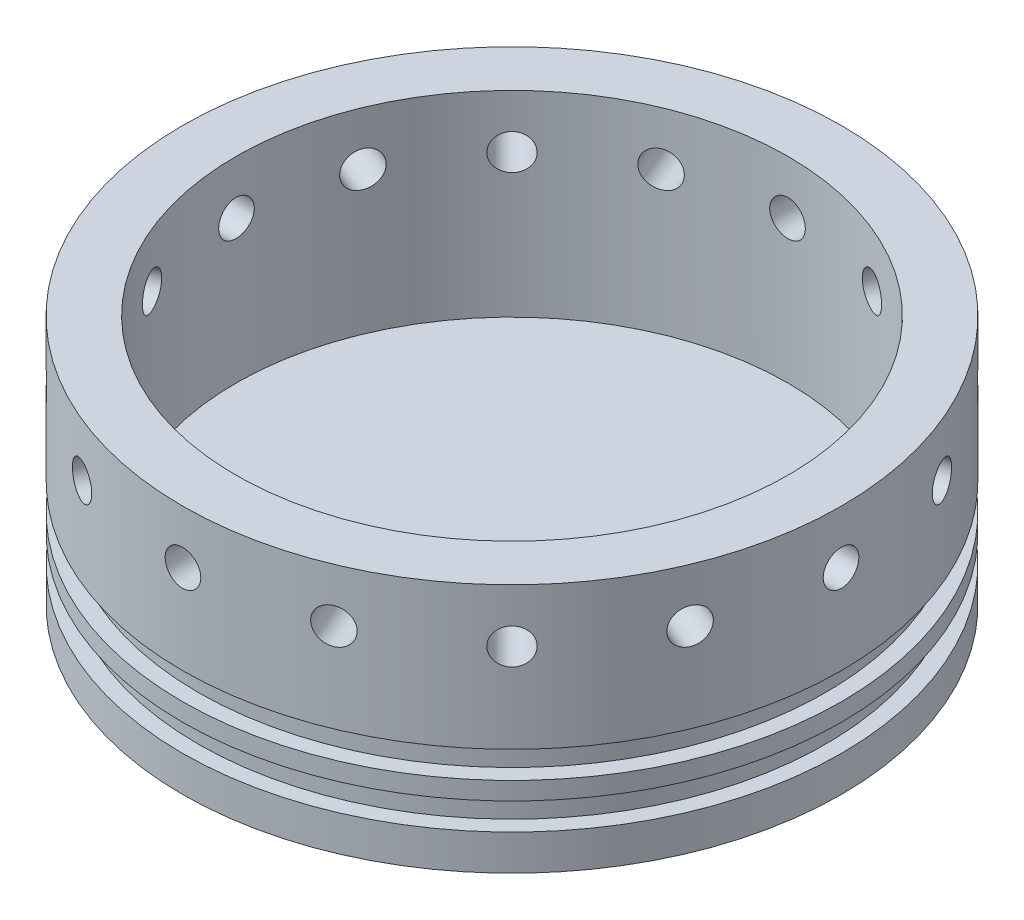
SolidWorks part; units mm, degrees
material "6061-T6 (SS)"
ref_plane "Front Plane" through (0, 0, 0) normal (0, 0, 1) x (1, 0, 0)
ref_plane "Top Plane" through (0, 0, 0) normal (0, 1, 0) x (1, 0, 0)
ref_plane "Right Plane" through (0, 0, 0) normal (1, 0, 0) x (0, 0, -1)
sketch "Sketch1" plane through (0, 0, 0) normal (0, 0, 1) x (1, 0, 0)
  line L1 (0, 0) -> (58.7375, 0)
  line L2 (58.7375, 0) -> (58.7375, 50.8) construction
  line L3 (0, 44.5262) -> (9.525, 44.5262)
  line L4 (58.7375, 0) -> (58.7375, 9.525)
  line L5 (58.7375, 9.525) -> (9.525, 9.525)
  line L6 (9.525, 9.525) -> (9.525, 44.5262)
  line L8 (0, 0) -> (0, 6.35)
  line L9 (0, 6.35) -> (2.8194, 6.35)
  line L10 (2.8194, 6.35) -> (2.8194, 11.1506)
  line L11 (2.8194, 11.1506) -> (0, 11.1506)
  line L15 (0, 11.1506) -> (0, 14.3256)
  line L16 (0, 14.3256) -> (2.8194, 14.3256)
  line L17 (2.8194, 14.3256) -> (2.8194, 19.1262)
  line L18 (2.8194, 19.1262) -> (0, 19.1262)
  line L19 (0, 19.1262) -> (0, 44.5262)
  dimension "D1" = 3.175
  dimension "D2" = 58.7375
  dimension "D3" = 9.525
  dimension "D4" = 6.35
  dimension "D5" = 4.8006
  dimension "D6" = 2.8194
  dimension "D7" = 4.8006
  dimension "D8" = 2.8194
  dimension "D9" = 2.8194
  dimension "D10" = 25.4
  dimension "D11" = 9.525
revolve "Revolve1" add sketch "Sketch1" angle 360 about L2 region at (0.7371, 3.175, 0)
ref_plane "HoleReferencePlane" through (0, 0, 58.7375) normal (0, 0, 1) x (1, 0, 0)
sketch "HoleReferencePoint" plane through (0, 0, 58.7375) normal (0, 0, 1) x (1, 0, 0)
  line L0 (107.95, 44.5262) -> (9.525, 44.5262) construction
  point P0 (58.7375, 35.0012)
  dimension "D1" = 9.525
hole_wizard "ForwardClosureHoles" positions "Sketch3" profile "Sketch5" hole size "1/4" standard "ANSI Inch" end condition through all
sketch "Sketch3" plane through (0, 0, 58.7375) normal (0, 0, 1) x (1, 0, 0)
  point P0 (58.7375, 35.0012)
sketch "Sketch5" plane through (58.7375, 35.0012, 58.7375) normal (1, 0, 0) x (0, -1, 0)
  line L0 (0, 0) -> (0, 117.475)
  line L1 (0, 117.475) -> (3.175, 117.475)
  line L2 (3.175, 117.475) -> (3.175, 0)
  line L5 (3.175, 0) -> (0, 0)
  line L11 (0, -6.35) -> (0, 107.95) construction
  dimension "Thru Hole Dia." = 6.35
  dimension "Thru Hole Depth" = 117.475
sketch "Centerline" plane through (0, 0, 0) normal (0, 0, 1) x (1, 0, 0)
  line L0 (58.7375, 44.5262) -> (58.7375, 0) construction
  line L1 (117.475, 44.5262) -> (0, 44.5262) construction
  line L2 (0, 0) -> (117.475, 0) construction
pattern_circular "HolePattern" count 16 over 360 about axis through (58.7375, 44.5262, 0) along (0, -1, 0) of "ForwardClosureHoles"
ref_plane "HoleAlignmentPlane" through (0, 35.0012, 0) normal (0, 1, 0) x (1, 0, 0)
